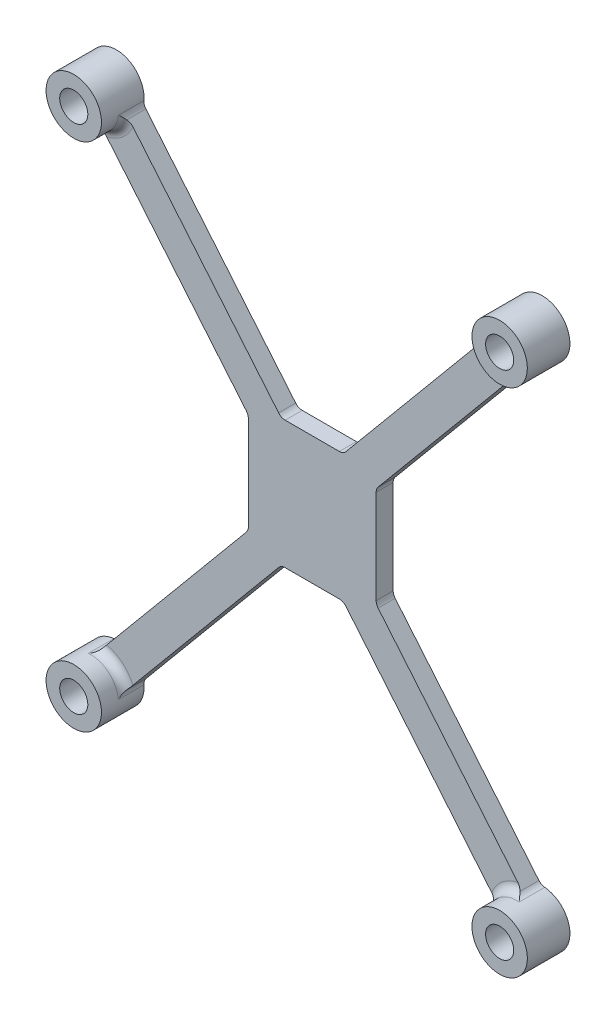
SolidWorks part; units mm, degrees
ref_plane "Спереди" through (0, 0, 0) normal (0, 0, 1) x (1, 0, 0)
ref_plane "Сверху" through (0, 0, 0) normal (0, 1, 0) x (1, 0, 0)
ref_plane "Справа" through (0, 0, 0) normal (1, 0, 0) x (0, 0, -1)
ref_plane "Плоскость4" through (0, -30, 0) normal (0, -1, 0) x (1, 0, 0)
sketch "Эскиз1" plane through (0, -30, 0) normal (0, -1, 0) x (1, 0, 0)
  line L0 (28.25, 5) -> (25, 5)
  line L1 (25, 5) -> (25, 0)
  line L2 (25, 0) -> (28.25, 0)
  line L3 (28.25, 0) -> (28.25, 5)
  line L4 (25, 5) -> (25, 0) construction
revolve "Повернуть1" add sketch "Эскиз1" angle 360 about L4 reverse direction yes
ref_plane "Плоскость5" through (0, 0, 0) normal (0, 0, -1) x (-1, 0, 0)
sketch "Эскиз2" plane through (0, 0, 0) normal (0, 0, -1) x (-1, 0, 0)
  line L0 (-7.5, -5.8759) -> (-24.8965, -26.7516)
  line L1 (-21.8236, -29.3124) -> (-3.6466, -7.5)
  line L2 (-3.6466, -7.5) -> (3.6466, -7.5)
  line L3 (3.6466, -7.5) -> (21.8236, -29.3124)
  line L4 (24.8965, -26.7516) -> (7.5, -5.8759)
  line L5 (7.5, -5.8759) -> (7.5, 5.8759)
  line L6 (7.5, 5.8759) -> (24.8965, 26.7516)
  line L7 (21.8236, 29.3124) -> (3.6466, 7.5)
  line L8 (3.6466, 7.5) -> (-3.6466, 7.5)
  line L9 (-3.6466, 7.5) -> (-21.8236, 29.3124)
  line L10 (-24.8965, 26.7516) -> (-7.5, 5.8759)
  line L11 (-7.5, 5.8759) -> (-7.5, -5.8759)
  arc A0 (-24.8965, -26.7516) -> (-21.8236, -29.3124) centre (-25, -30) cw
  arc A1 (21.8236, -29.3124) -> (24.8965, -26.7516) centre (25, -30) ccw
  arc A2 (24.8965, 26.7516) -> (21.8236, 29.3124) centre (25, 30) ccw
  arc A3 (-21.8236, 29.3124) -> (-24.8965, 26.7516) centre (-25, 30) ccw
extrude "Бобышка-Вытянуть1" add sketch "Эскиз2" against normal blind 2
sketch "Эскиз3" plane through (0, 0, 2) normal (0, 0, 1) x (1, 0, 0)
  circle A0 centre (-25, 30) radius 3.25
extrude "Бобышка-Вытянуть2" add sketch "Эскиз3" along normal blind 3
sketch "Эскиз4" plane through (0, 0, 2) normal (0, 0, 1) x (1, 0, 0)
  circle A0 centre (25, 30) radius 3.25
extrude "Бобышка-Вытянуть3" add sketch "Эскиз4" along normal blind 3
sketch "Эскиз5" plane through (0, 0, 2) normal (0, 0, 1) x (1, 0, 0)
  circle A0 centre (-25, -30) radius 3.25
extrude "Бобышка-Вытянуть4" add sketch "Эскиз5" along normal blind 3
hole_wizard "Диаметр отверстия Ø3.3 (3.3)1" positions "Эскиз7" profile "Эскиз6" hole size "Ø3.3" standard "Ansi Metric"
sketch "Эскиз7" plane through (0, 0, 5) normal (0, 0, 1) x (1, 0, 0)
  point P0 (25, -30)
  point P1 (-25, 30)
  point P2 (25, 30)
  point P3 (-25, -30)
sketch "Эскиз6" plane through (25, -30, 5) normal (1, 0, 0) x (0, -1, 0)
  line L0 (0, 0) -> (0, 5)
  line L1 (0, 5) -> (1.65, 5)
  line L2 (1.65, 5) -> (1.65, 0)
  line L5 (1.65, 0) -> (0, 0)
  line L11 (0, -6.35) -> (0, 107.95) construction
  dimension "Диаметр сквозного отверстия" = 3.3
  dimension "Глубина сквозного отверстия" = 5
fillet "Скругление1" radius 1 20 edges at (24.8965, -26.7516, 1) (21.8236, -29.3124, 1) (22.9194, -27.5033, 2) (-21.8236, -29.3124, 1) (-22.9194, -27.5033, 2) (-24.8965, -26.7516, 1) (7.5, -5.8759, 1) (21.8236, 29.3124, 1) (24.8965, 26.7516, 1) (22.9194, 27.5033, 2) (-3.6466, -7.5, 1) (3.6466, 7.5, 1) (-3.6466, 7.5, 1) (-24.8965, 26.7516, 1) (-22.9194, 27.5033, 2) (-21.8236, 29.3124, 1) (3.6466, -7.5, 1) (7.5, 5.8759, 1) (-7.5, 5.8759, 1) (-7.5, -5.8759, 1) tangent propagation no
